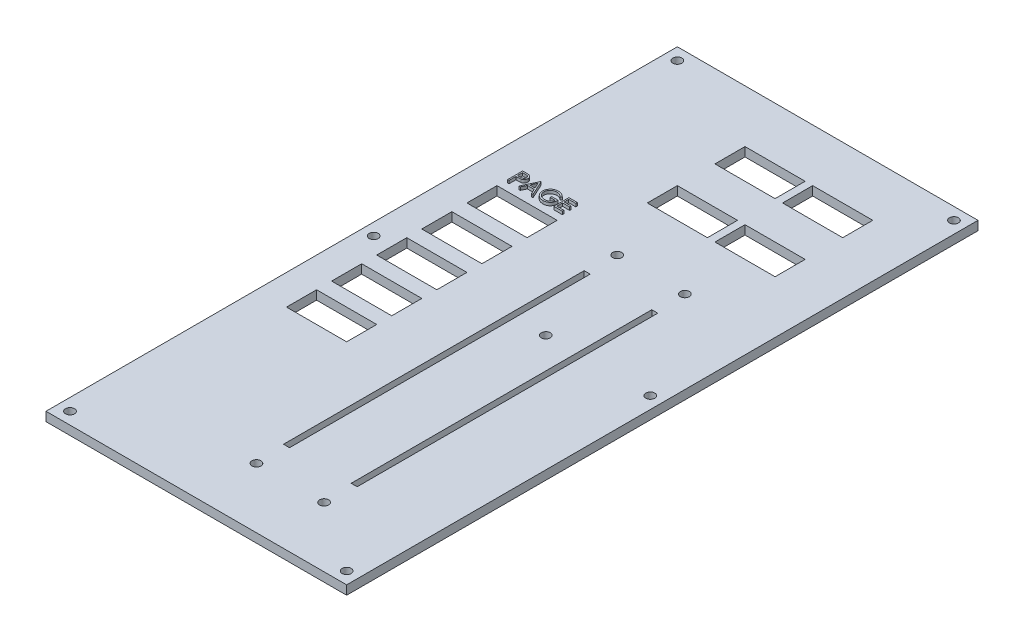
SolidWorks part; units mm, degrees
ref_plane "Front Plane" through (0, 0, 0) normal (0, 0, 1) x (1, 0, 0)
ref_plane "Top Plane" through (0, 0, 0) normal (0, 1, 0) x (1, 0, 0)
ref_plane "Right Plane" through (0, 0, 0) normal (1, 0, 0) x (0, 0, -1)
sketch "Sketch1" plane through (0, 0, 0) normal (0, 1, 0) x (1, 0, 0)
  line L1 (-50, -105) -> (50, -105)
  line L2 (-50, -105) -> (-50, 105)
  line L3 (-50, 105) -> (50, 105)
  line L4 (50, -105) -> (50, 105)
  line L5 (-50, -105) -> (50, 105) construction
  line L6 (-50, 105) -> (50, -105) construction
  point P0 (0, 0)
  dimension "D1" = 210
  dimension "D2" = 100
extrude "Boss-Extrude1" add sketch "Sketch1" along normal blind 3 contours L2 L3 L4 L1
sketch "Sketch3" plane through (0, 3, 0) normal (0, 1, 0) x (1, 0, 0)
  line L0 (-1, 25) -> (1, 25)
  line L1 (-1, 25) -> (-1, -75)
  line L2 (-1, -75) -> (1, -75)
  line L3 (1, 25) -> (1, -75)
  line L4 (-1, 25) -> (1, -75) construction
  line L5 (-1, -75) -> (1, 25) construction
  line L6 (-50, -105) -> (-50, 105) construction
  circle A0 centre (0, -85) radius 1.5
  circle A1 centre (0, 35) radius 1.5
  point P0 (0, -25)
  dimension "D3" = 3
  dimension "D4" = 3
  dimension "D1" = 100
  dimension "D2" = 2
  dimension "D5" = 120
  dimension "D6" = 60
  dimension "D7" = 50
  dimension "D8" = 25
extrude "Cut-Extrude1" cut sketch "Sketch3" against normal up to next
pattern_linear "LPattern1" count 2 spacing 22.5 along (1, 0, 0) of "Cut-Extrude1"
sketch "Sketch4" plane through (0, 3, 0) normal (0, 1, 0) x (1, 0, 0)
  line L1 (-10, 55) -> (10, 55)
  line L2 (-10, 55) -> (-10, 65)
  line L3 (-10, 65) -> (10, 65)
  line L4 (10, 55) -> (10, 65)
  line L5 (-10, 55) -> (10, 65) construction
  line L6 (-10, 65) -> (10, 55) construction
  circle A0 centre (0, 35) radius 1.5 construction
  point P0 (0, 60)
  dimension "D1" = 10
  dimension "D2" = 20
  dimension "D3" = 25
extrude "Cut-Extrude2" cut sketch "Sketch4" against normal up to next
pattern_linear "LPattern2" count 2 spacing 22.5 along (1, 0, 0) count 2 spacing 22.5 along (0, 0, -1) of "Cut-Extrude2"
sketch "Sketch5" plane through (0, 3, 0) normal (0, 1, 0) x (1, 0, 0)
  line L0 (-50, 105) -> (50, 105) construction
  line L1 (-50, -105) -> (-50, 105) construction
  line L2 (50, -105) -> (50, 105) construction
  line L3 (-50, -105) -> (50, -105) construction
  circle A0 centre (-46, 101) radius 1.5
  circle A1 centre (46, 101) radius 1.5
  circle A2 centre (46, -101) radius 1.5
  circle A3 centre (-46, -101) radius 1.5
  circle A4 centre (11.25, 0) radius 1.5
  dimension "D1" = 3
  dimension "D4" = 3
  dimension "D9" = 3
  dimension "D10" = 3
  dimension "D13" = 3
  dimension "D2" = 4
  dimension "D3" = 4
  dimension "D5" = 4
  dimension "D6" = 4
  dimension "D7" = 4
  dimension "D8" = 4
  dimension "D11" = 4
  dimension "D12" = 4
  dimension "D14" = 11.25
extrude "Cut-Extrude3" cut sketch "Sketch5" against normal up to next
sketch "Sketch6" plane through (0, 3, 0) normal (0, 1, 0) x (1, 0, 0)
  line L0 (-50, -105) -> (-50, 105) construction
  line L1 (-40, 35) -> (-20, 35)
  line L2 (-40, 35) -> (-40, 25)
  line L3 (-40, 25) -> (-20, 25)
  line L4 (-20, 35) -> (-20, 25)
  line L5 (-40, 35) -> (-20, 25) construction
  line L6 (-40, 25) -> (-20, 35) construction
  point P0 (-30, 30)
  dimension "D1" = 20
  dimension "D2" = 10
  dimension "D3" = 20
  dimension "D4" = 30
extrude "Cut-Extrude4" cut sketch "Sketch6" against normal up to next
pattern_linear "LPattern3" count 5 spacing 15 along (0, 0, 1) of "Cut-Extrude4"
sketch "Sketch7" plane through (0, 3, 0) normal (0, 1, 0) x (1, 0, 0)
  line L0 (-50, -105) -> (-50, 105) construction
  circle A0 centre (-46, 0) radius 1.5
  dimension "D1" = 3
  dimension "D2" = 4
extrude "Cut-Extrude5" cut sketch "Sketch7" against normal up to next
sketch "Sketch8" plane through (0, 3, 0) normal (0, 1, 0) x (1, 0, 0)
  line L0 (50, -105) -> (50, 105) construction
  circle A0 centre (46, 0) radius 1.5
  dimension "D1" = 3
  dimension "D2" = 4
extrude "Cut-Extrude6" cut sketch "Sketch8" against normal up to next
sketch "Sketch10" plane through (0, 3, 0) normal (0, 1, 0) x (1, 0, 0)
  text T0 "PAGE" font "Century Gothic" height 5
  dimension "D1" = 0.4
  dimension "D2" = 2.5
extrude "Boss-Extrude2" add sketch "Sketch10" along normal blind 1
ref_plane "Plane1" through (-50, 3, 105) normal (0, 0, -1) x (-1, 0, 0)
